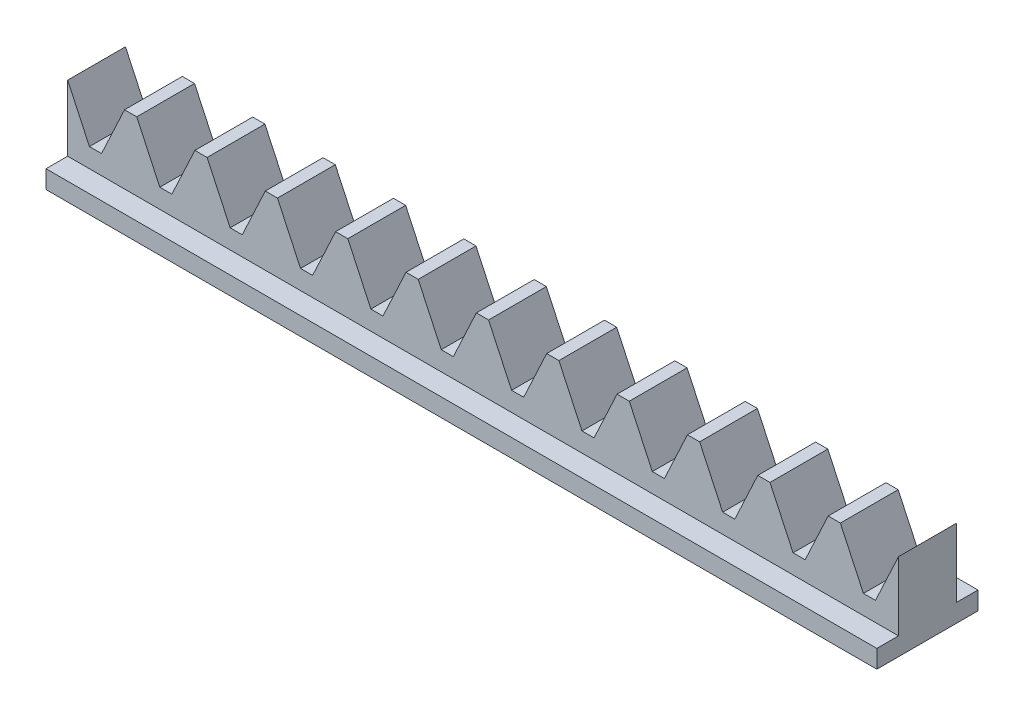
SolidWorks part; units mm, degrees
ref_plane "Front Plane" through (0, 0, 0) normal (0, 0, 1) x (1, 0, 0)
ref_plane "Top Plane" through (0, 0, 0) normal (0, 1, 0) x (1, 0, 0)
ref_plane "Right Plane" through (0, 0, 0) normal (1, 0, 0) x (0, 0, -1)
sketch "Sketch1" plane through (0, 0, 0) normal (0, 0, 1) x (1, 0, 0)
  circle A0 centre (0, 0) radius 32.55
  circle A1 centre (0, 0) radius 35.65
  circle A2 centre (0, 0) radius 28.675
  dimension "D1" = 65.1
  dimension "D2" = 71.3
  dimension "D3" = 6.975
sketch "Sketch9" plane through (0, 0, 0) normal (0, 0, 1) x (1, 0, 0)
  line L0 (49.45, 6) -> (52.64, -0.841)
  line L1 (-57.5, 6) -> (57.5, 6)
  line L2 (-57.5, 6) -> (-57.5, -6)
  line L3 (-57.5, -6) -> (57.5, -6)
  line L4 (57.5, 6) -> (57.5, -6)
  line L5 (-57.5, 6) -> (57.5, -6) construction
  line L6 (-57.5, -6) -> (57.5, 6) construction
  line L7 (52.64, -0.841) -> (54.31, -0.841)
  line L8 (57.5, 6) -> (54.31, -0.841)
  line L9 (53.475, -0.841) -> (53.475, 7.325) construction
  line L10 (51.045, 2.5795) -> (55.905, 2.5795) construction
  point P0 (0, 0)
  dimension "D1" = 115
  dimension "D2" = 12
  dimension "D3" = 3.4205
  dimension "D4" = 3.4205
  dimension "D5" = 25
  dimension "D6" = 4.86
  dimension "D7" = 2.43
extrude "Boss-Extrude4" add sketch "Sketch9" along normal mid plane 8 contours L8 L1 L0 L7 | L1 L8 L7 L0 L2 L3 L4 region at (53.475, 3.3279, 0) region at (-1.3201, -0.0822, 0)
extrude "Cut-Extrude7" cut sketch "Sketch9<4>" against normal through all both and the other way through all contours L8 L1 L0 L7 region at (53.475, 3.3279, 0)
sketch "Sketch9<4>" plane through (0, 0, 0) normal (0, 0, 1) x (1, 0, 0) same geometry as "Sketch9"
pattern_linear "LPattern2" count 13 spacing 9.7389 along (-1, 0, 0) of "Cut-Extrude7"
sketch "Sketch10" plane through (-57.5, 0, 0) normal (-1, 0, 0) x (0, 0, 1)
  line L0 (4, 5.6185) -> (4, -6) construction
  line L1 (7, -6) -> (-7, -6)
  line L2 (7, -6) -> (7, -3.5)
  line L3 (7, -3.5) -> (-7, -3.5)
  line L4 (-7, -6) -> (-7, -3.5)
  dimension "D1" = 2.5
  dimension "D2" = 14
  dimension "D3" = 3
extrude "Boss-Extrude5" add sketch "Sketch10" against normal up to surface (115 mm away) up to face at (57.5, 0, 0)
equation "\"Module\"= 3.1mm"
equation "\"Number of Teeth\"= 21"
equation "\"D1@Sketch1\"=\"Module\" * \"Number of Teeth\""
equation "\"D2@Sketch1\"=(\"Number of Teeth\" + 2) * \"Module\""
equation "\"D3@Sketch1\"=\"Module\" * if(\"Module\"=>1.25,2.25,2.4)"
equation "\"D5@Sketch4\"= 180 / \"Number of Teeth\""
equation "\"D1@Fillet1\"= .3 * \"Module\""
equation "\"D1@CirPattern1\"= \"Number of Teeth\""
